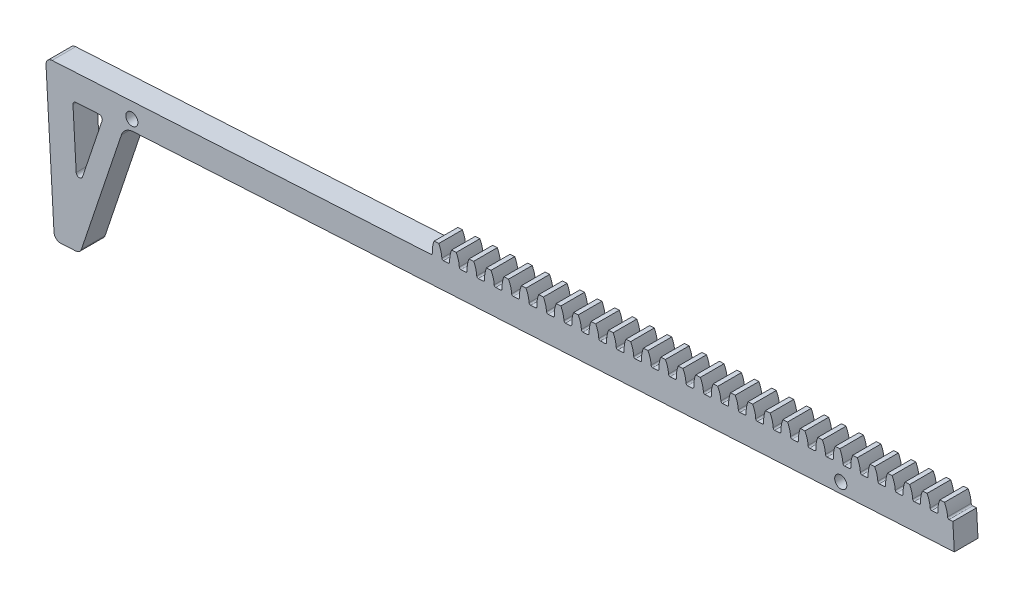
SolidWorks part; units mm, degrees
ref_plane "Front Plane" through (0, 0, 0) normal (0, 0, 1) x (1, 0, 0)
ref_plane "Top Plane" through (0, 0, 0) normal (0, 1, 0) x (1, 0, 0)
ref_plane "Right Plane" through (0, 0, 0) normal (1, 0, 0) x (0, 0, -1)
sketch "Sketch1" plane through (0, 0, 0) normal (0, 0, 1) x (1, 0, 0)
  circle A0 centre (0, 0) radius 23.4
  circle A1 centre (0, 0) radius 24.7
  circle A2 centre (0, 0) radius 21.58
  dimension "D1" = 46.8
  dimension "D2" = 49.4
  dimension "D3" = 3.12
extrude "Boss-Extrude1" add sketch "Sketch1" along normal mid plane 5.642 contours A2 | A0 A2 | A1 A0 region at (-22.7381, 0, 0) region at (-24.0014, 0, 0) region at (0, 0, 0)
sketch "Sketch3" plane through (0, 0, 2.821) normal (0, 0, 1) x (1, 0, 0)
  line L0 (0, 0) -> (0, 24.7) construction
  line L1 (-1.0207, 23.3777) -> (1.0207, 23.3777) construction
  line L2 (0, 0) -> (-0.7079, 21.5684) construction
  line L3 (0, 20.5885) -> (-1.8365, 25.6343) construction
  line L4 (0, 0) -> (2.1527, 24.606) construction
  line L5 (1.0207, 23.3777) -> (3.0543, 23.1998) construction
  circle A0 centre (0, 0) radius 24.7 construction
  arc A1 (-2.2399, 25.6022) -> (-0.7079, 21.5684) centre (-7.3591, 21.3501) cw
  arc A2 (2.2399, 25.6022) -> (0.7079, 21.5684) centre (7.3591, 21.3501) ccw
  circle A3 centre (0, 0) radius 21.58 construction
  arc A4 (0.7079, 21.5684) -> (-0.7079, 21.5684) centre (0, 0) ccw
  circle A6 centre (0, 0) radius 23.4 construction
  circle A7 centre (0, 0) radius 25.7
  arc A8 (2.2399, 25.6022) -> (-2.2399, 25.6022) centre (0, 0) ccw
  circle A9 centre (0, 0) radius 24.7 construction
  point P20 (2.0375, 23.2888)
  dimension "D2" = 20
  dimension "D3" = 5
sketch "Sketch4" plane through (0, 0, 0) normal (0, 1, 0) x (1, 0, 0)
  line L0 (0.7559, -2.821) -> (-0.7559, 2.821)
  line L1 (-24.7, -2.821) -> (24.7, -2.821) construction
  line L2 (24.7, 2.821) -> (-24.7, 2.821) construction
  line L3 (0, -3.2131) -> (0, 3.2131) construction
  dimension "D1" = 15
curve "Curve1"
sketch "Sketch5" plane through (0, 0, 2.821) normal (0, 0, 1) x (0.9995, -0.0306, 0)
  line L0 (0, 0) -> (0, 24.7) construction
  line L1 (-1.0207, 23.3777) -> (1.0207, 23.3777) construction
  line L2 (0, 0) -> (-0.7079, 21.5684) construction
  line L3 (0, 20.5885) -> (-1.8365, 25.6343) construction
  line L4 (0, 0) -> (2.1527, 24.606) construction
  line L5 (1.0207, 23.3777) -> (3.0543, 23.1998) construction
  arc A1 (-2.2399, 25.6022) -> (-0.7079, 21.5684) centre (-7.3591, 21.3501) cw
  arc A2 (2.2399, 25.6022) -> (0.7079, 21.5684) centre (7.3591, 21.3501) ccw
  arc A4 (0.7079, 21.5684) -> (-0.7079, 21.5684) centre (0, 0) ccw
  arc A8 (2.2399, 25.6022) -> (-2.2399, 25.6022) centre (0, 0) ccw
  point P20 (2.0375, 23.2888)
sketch "Sketch7" [suppressed] plane through (1.6622, 0.2826, -4.7625) normal (0, 0, 1) x (0.9724, 0.2332, 0)
  line L0 (0, 0) -> (0, 12.6) construction
  line L1 (-1.4097, 10.7076) -> (1.4097, 10.7076) construction
  line L2 (0, 0) -> (-0.707, 8.2498) construction
  line L3 (0, 6.9803) -> (-2.3358, 13.3979) construction
  line L4 (0, 0) -> (3.2611, 12.1707) construction
  line L5 (1.4097, 10.7076) -> (4.133, 9.9779) construction
  arc A1 (-3.5199, 13.1366) -> (-0.707, 8.2498) centre (-7.3467, 7.6808) cw
  arc A2 (3.5199, 13.1366) -> (0.707, 8.2498) centre (7.3467, 7.6808) ccw
  arc A4 (0.707, 8.2498) -> (-0.707, 8.2498) centre (0, 0) ccw
  arc A8 (3.5199, 13.1366) -> (-3.5199, 13.1366) centre (0, 0) ccw
  point P20 (2.7713, 10.3428)
loft "Cut-Loft1" [suppressed] cut profiles "Sketch7", "Sketch3" end constraint default
fillet "Fillet2" [suppressed] radius 0.39
pattern_circular "CirPattern2" [suppressed] count 36 over 360 of bodies 104
sketch "Sketch8" plane through (0, 0, 2.821) normal (0, 0, 1) x (1, 0, 0)
  line L0 (0, 24.7) -> (0, -24.7) construction
  line L1 (0, 0) -> (7.9375, 0) construction
  circle A0 centre (0, 0) radius 7.9375
  circle A1 centre (0, 0) radius 24.7 construction
  circle A2 centre (0, 13.5) radius 1.7526
  circle A3 centre (11.6913, 6.75) radius 1.7526
  circle A4 centre (11.6913, -6.75) radius 1.7526
  circle A5 centre (0, -13.5) radius 1.7526
  circle A6 centre (-11.6913, -6.75) radius 1.7526
  circle A7 centre (-11.6913, 6.75) radius 1.7526
  spline S0 degree 3 poles (-0.7559, 24.6884) (-0.252, 24.7039) (0.252, 24.7039) (0.7559, 24.6884) knots 0 0 0 0 1 1 1 1 weights 1 0.999688 0.999688 1 construction
  point P26 (0, 0)
  dimension "D1" = 15.875
  dimension "D2" = 13.5
  dimension "D3" = 3.5052
  dimension "D4" = 6
extrude "Cut-Extrude1" cut sketch "Sketch8" against normal through all
extrude "Cut-Extrude2" cut sketch "Sketch5" against normal through all
fillet "Fillet3" radius 0.39 2 edges at (-0.0475, 21.5799, 0) (1.3676, 21.5366, 0)
pattern_circular "CirPattern3" count 36 over 360 about axis through (0, 0, 2.821) along (0, 0, -1) of "Cut-Extrude2", "Fillet3"
sketch "Sketch9" plane through (0, 0, 2.821) normal (0, 0, 1) x (1, 0, 0)
  line L0 (0, 0) -> (0, 11.1125) construction
  line L1 (0, 0) -> (9.6237, 5.5563) construction
  circle A0 centre (0, 0) radius 11.1125 construction
  circle A1 centre (0, 0) radius 19.05 construction
  circle A2 centre (0, 13.5) radius 2.994
  circle A3 centre (11.6913, 6.75) radius 2.994
  circle A4 centre (11.6913, -6.75) radius 2.994
  circle A5 centre (0, -13.5) radius 2.994
  circle A6 centre (-11.6913, -6.75) radius 2.994
  circle A7 centre (-11.6913, 6.75) radius 2.994
  point P23 (0, 0)
  dimension "D1" = 22.225
  dimension "D3" = 5.988
  dimension "D2" = 7.9375
  dimension "D4" = 6
extrude "Cut-Extrude3" cut sketch "Sketch9" against normal blind 1.292
chamfer "Chamfer1" distance 0.2 angle 45 8 edges at (7.9375, 0, 2.821) (7.9375, 0, -2.821) (-9.9387, -6.75, 1.529) (1.7526, -13.5, 1.529) (13.4439, -6.75, 1.529) (13.4439, 6.75, 1.529) (1.7526, 13.5, 1.529) (-9.9387, 6.75, 1.529)
sketch "Sketch11" plane through (0, 0, 2.821) normal (0, 0, 1) x (1, 0, 0)
  line L0 (-2.4235, 21.8111) -> (-0.0583, 21.9452) construction
  line L1 (0.3252, 21.5775) -> (1.541, 21.6465)
  line L2 (4.6292, 21.8217) -> (5.8451, 21.8906)
  line L3 (8.9332, 22.0658) -> (10.1491, 22.1348)
  line L4 (13.2372, 22.3099) -> (14.4531, 22.3789)
  line L5 (17.5413, 22.554) -> (18.7571, 22.623)
  line L6 (21.8453, 22.7982) -> (23.0612, 22.8671)
  line L7 (26.1493, 23.0423) -> (27.3652, 23.1113)
  line L8 (30.4533, 23.2864) -> (31.6692, 23.3554)
  line L9 (34.7574, 23.5305) -> (35.9732, 23.5995)
  line L10 (39.0614, 23.7747) -> (40.2773, 23.8436)
  line L11 (43.3654, 24.0188) -> (44.5813, 24.0877)
  line L12 (47.6695, 24.2629) -> (48.8853, 24.3319)
  line L13 (51.9735, 24.507) -> (53.1893, 24.576)
  line L14 (56.2775, 24.7512) -> (57.4934, 24.8201)
  line L15 (60.5815, 24.9953) -> (61.7974, 25.0642)
  line L16 (64.8856, 25.2394) -> (66.1014, 25.3084)
  line L17 (69.1896, 25.4835) -> (70.4054, 25.5525)
  line L18 (73.4936, 25.7276) -> (74.7095, 25.7966)
  line L19 (77.7976, 25.9718) -> (79.0135, 26.0407)
  line L20 (82.1017, 26.2159) -> (83.3175, 26.2849)
  line L21 (86.4057, 26.46) -> (87.6215, 26.529)
  line L22 (90.7097, 26.7041) -> (91.9256, 26.7731)
  line L23 (95.0137, 26.9483) -> (96.2296, 27.0172)
  line L24 (99.3178, 27.1924) -> (100.5336, 27.2613)
  line L25 (103.6218, 27.4365) -> (104.8376, 27.5055)
  line L26 (107.9258, 27.6806) -> (109.1417, 27.7496)
  line L27 (112.2298, 27.9248) -> (113.4457, 27.9937)
  line L28 (116.5339, 28.1689) -> (117.7497, 28.2378)
  line L29 (120.8379, 28.413) -> (122.0537, 28.482)
  line L30 (125.1419, 28.6571) -> (126.3578, 28.7261)
  line L31 (129.4459, 28.9012) -> (130.6618, 28.9702)
  line L32 (133.75, 29.1454) -> (134.9658, 29.2143)
  line L33 (138.054, 29.3895) -> (139.2698, 29.4585)
  line L34 (142.358, 29.6336) -> (143.5739, 29.7026)
  line L35 (146.662, 29.8777) -> (147.8779, 29.9467)
  line L36 (150.9661, 30.1219) -> (152.1819, 30.1908)
  line L37 (-2.763, 21.4024) -> (-2.4034, 15.0626)
  line L38 (155.2701, 30.366) -> (156.4859, 30.435)
  line L39 (159.5741, 30.6101) -> (160.79, 30.6791)
  line L40 (163.8781, 30.8542) -> (165.094, 30.9232)
  line L41 (168.1822, 31.0984) -> (169.398, 31.1673)
  line L42 (172.4862, 31.3425) -> (173.702, 31.4114)
  line L43 (-2.4034, 15.0626) -> (177.1498, 25.2468)
  line L44 (177.1498, 25.2468) -> (176.7902, 31.5866)
  arc A0 (1.541, 21.6465) -> (1.8805, 22.0552) centre (1.4911, 22.0333) ccw
  arc A1 (2.332, 24.8653) -> (1.8805, 22.0552) centre (8.5248, 22.429) ccw
  arc A2 (3.4794, 24.9304) -> (2.332, 24.8653) centre (4.304, 0.2441) ccw
  arc A3 (4.2457, 22.1894) -> (3.4794, 24.9304) centre (-2.3982, 21.8094) ccw
  arc A4 (4.2457, 22.1894) -> (4.6292, 21.8217) centre (4.6351, 22.2116) ccw
  arc A5 (5.8451, 21.8906) -> (6.1845, 22.2993) centre (5.7951, 22.2774) ccw
  arc A6 (6.636, 25.1094) -> (6.1845, 22.2993) centre (12.8288, 22.6731) ccw
  arc A7 (7.7834, 25.1745) -> (6.636, 25.1094) centre (8.6081, 0.4882) ccw
  arc A8 (8.5497, 22.4335) -> (7.7834, 25.1745) centre (1.9058, 22.0536) ccw
  arc A9 (8.5497, 22.4335) -> (8.9332, 22.0658) centre (8.9391, 22.4558) ccw
  arc A10 (10.1491, 22.1348) -> (10.4885, 22.5435) centre (10.0992, 22.5215) ccw
  arc A11 (10.94, 25.3535) -> (10.4885, 22.5435) centre (17.1328, 22.9172) ccw
  arc A12 (12.0874, 25.4186) -> (10.94, 25.3535) centre (12.9121, 0.7324) ccw
  arc A13 (12.8538, 22.6776) -> (12.0874, 25.4186) centre (6.2098, 22.2977) ccw
  arc A14 (12.8538, 22.6776) -> (13.2372, 22.3099) centre (13.2431, 22.6999) ccw
  arc A15 (14.4531, 22.3789) -> (14.7926, 22.7876) centre (14.4032, 22.7657) ccw
  arc A16 (15.2441, 25.5976) -> (14.7926, 22.7876) centre (21.4368, 23.1613) ccw
  arc A17 (16.3914, 25.6627) -> (15.2441, 25.5976) centre (17.2161, 0.9765) ccw
  arc A18 (17.1578, 22.9217) -> (16.3914, 25.6627) centre (10.5139, 22.5418) ccw
  arc A19 (17.1578, 22.9217) -> (17.5413, 22.554) centre (17.5472, 22.944) ccw
  arc A20 (18.7571, 22.623) -> (19.0966, 23.0317) centre (18.7072, 23.0098) ccw
  arc A21 (19.5481, 25.8418) -> (19.0966, 23.0317) centre (25.7409, 23.4055) ccw
  arc A22 (20.6955, 25.9068) -> (19.5481, 25.8418) centre (21.5201, 1.2206) ccw
  arc A23 (21.4618, 23.1659) -> (20.6955, 25.9068) centre (14.8179, 22.7859) ccw
  arc A24 (21.4618, 23.1659) -> (21.8453, 22.7982) centre (21.8512, 23.1881) ccw
  arc A25 (23.0612, 22.8671) -> (23.4006, 23.2758) centre (23.0112, 23.2539) ccw
  arc A26 (23.8521, 26.0859) -> (23.4006, 23.2758) centre (30.0449, 23.6496) ccw
  arc A27 (24.9995, 26.151) -> (23.8521, 26.0859) centre (25.8242, 1.4647) ccw
  arc A28 (25.7658, 23.41) -> (24.9995, 26.151) centre (19.1219, 23.03) ccw
  arc A29 (25.7658, 23.41) -> (26.1493, 23.0423) centre (26.1552, 23.4322) ccw
  arc A30 (27.3652, 23.1113) -> (27.7046, 23.5199) centre (27.3153, 23.498) ccw
  arc A31 (28.1561, 26.33) -> (27.7046, 23.5199) centre (34.3489, 23.8937) ccw
  arc A32 (29.3035, 26.3951) -> (28.1561, 26.33) centre (30.1282, 1.7089) ccw
  arc A33 (30.0699, 23.6541) -> (29.3035, 26.3951) centre (23.4259, 23.2742) ccw
  arc A34 (30.0699, 23.6541) -> (30.4533, 23.2864) centre (30.4592, 23.6764) ccw
  arc A35 (31.6692, 23.3554) -> (32.0087, 23.7641) centre (31.6193, 23.7422) ccw
  arc A36 (32.4602, 26.5741) -> (32.0087, 23.7641) centre (38.6529, 24.1378) ccw
  arc A37 (33.6075, 26.6392) -> (32.4602, 26.5741) centre (34.4322, 1.953) ccw
  arc A38 (34.3739, 23.8982) -> (33.6075, 26.6392) centre (27.73, 23.5183) ccw
  arc A39 (34.3739, 23.8982) -> (34.7574, 23.5305) centre (34.7633, 23.9205) ccw
  arc A40 (35.9732, 23.5995) -> (36.3127, 24.0082) centre (35.9233, 23.9863) ccw
  arc A41 (36.7642, 26.8183) -> (36.3127, 24.0082) centre (42.957, 24.382) ccw
  arc A42 (37.9116, 26.8833) -> (36.7642, 26.8183) centre (38.7362, 2.1971) ccw
  arc A43 (38.6779, 24.1423) -> (37.9116, 26.8833) centre (32.034, 23.7624) ccw
  arc A44 (38.6779, 24.1423) -> (39.0614, 23.7747) centre (39.0673, 24.1646) ccw
  arc A45 (40.2773, 23.8436) -> (40.6167, 24.2523) centre (40.2273, 24.2304) ccw
  arc A46 (41.0682, 27.0624) -> (40.6167, 24.2523) centre (47.261, 24.6261) ccw
  arc A47 (42.2156, 27.1275) -> (41.0682, 27.0624) centre (43.0403, 2.4412) ccw
  arc A48 (42.9819, 24.3865) -> (42.2156, 27.1275) centre (36.338, 24.0065) ccw
  arc A49 (42.9819, 24.3865) -> (43.3654, 24.0188) centre (43.3713, 24.4087) ccw
  arc A50 (44.5813, 24.0877) -> (44.9207, 24.4964) centre (44.5314, 24.4745) ccw
  arc A51 (45.3722, 27.3065) -> (44.9207, 24.4964) centre (51.565, 24.8702) ccw
  arc A52 (46.5196, 27.3716) -> (45.3722, 27.3065) centre (47.3443, 2.6854) ccw
  arc A53 (47.286, 24.6306) -> (46.5196, 27.3716) centre (40.642, 24.2507) ccw
  arc A54 (47.286, 24.6306) -> (47.6695, 24.2629) centre (47.6753, 24.6529) ccw
  arc A55 (48.8853, 24.3319) -> (49.2248, 24.7406) centre (48.8354, 24.7187) ccw
  arc A56 (49.6763, 27.5506) -> (49.2248, 24.7406) centre (55.869, 25.1143) ccw
  arc A57 (50.8236, 27.6157) -> (49.6763, 27.5506) centre (51.6483, 2.9295) ccw
  arc A58 (51.59, 24.8747) -> (50.8236, 27.6157) centre (44.9461, 24.4948) ccw
  arc A59 (51.59, 24.8747) -> (51.9735, 24.507) centre (51.9794, 24.897) ccw
  arc A60 (53.1893, 24.576) -> (53.5288, 24.9847) centre (53.1394, 24.9628) ccw
  arc A61 (53.9803, 27.7948) -> (53.5288, 24.9847) centre (60.1731, 25.3585) ccw
  arc A62 (55.1277, 27.8598) -> (53.9803, 27.7948) centre (55.9523, 3.1736) ccw
  arc A63 (55.894, 25.1188) -> (55.1277, 27.8598) centre (49.2501, 24.7389) ccw
  arc A64 (55.894, 25.1188) -> (56.2775, 24.7512) centre (56.2834, 25.1411) ccw
  arc A65 (57.4934, 24.8201) -> (57.8328, 25.2288) centre (57.4434, 25.2069) ccw
  arc A66 (58.2843, 28.0389) -> (57.8328, 25.2288) centre (64.4771, 25.6026) ccw
  arc A67 (59.4317, 28.104) -> (58.2843, 28.0389) centre (60.2564, 3.4177) ccw
  arc A68 (60.198, 25.363) -> (59.4317, 28.104) centre (53.5541, 24.983) ccw
  arc A69 (60.198, 25.363) -> (60.5815, 24.9953) centre (60.5874, 25.3852) ccw
  arc A70 (61.7974, 25.0642) -> (62.1368, 25.4729) centre (61.7475, 25.451) ccw
  arc A71 (62.5883, 28.283) -> (62.1368, 25.4729) centre (68.7811, 25.8467) ccw
  arc A72 (63.7357, 28.3481) -> (62.5883, 28.283) centre (64.5604, 3.6618) ccw
  arc A73 (64.5021, 25.6071) -> (63.7357, 28.3481) centre (57.8581, 25.2272) ccw
  arc A74 (64.5021, 25.6071) -> (64.8856, 25.2394) centre (64.8914, 25.6294) ccw
  arc A75 (66.1014, 25.3084) -> (66.4409, 25.7171) centre (66.0515, 25.6952) ccw
  arc A76 (66.8924, 28.5271) -> (66.4409, 25.7171) centre (73.0851, 26.0908) ccw
  arc A77 (68.0397, 28.5922) -> (66.8924, 28.5271) centre (68.8644, 3.906) ccw
  arc A78 (68.8061, 25.8512) -> (68.0397, 28.5922) centre (62.1622, 25.4713) ccw
  arc A79 (68.8061, 25.8512) -> (69.1896, 25.4835) centre (69.1955, 25.8735) ccw
  arc A80 (70.4054, 25.5525) -> (70.7449, 25.9612) centre (70.3555, 25.9393) ccw
  arc A81 (71.1964, 28.7712) -> (70.7449, 25.9612) centre (77.3892, 26.335) ccw
  arc A82 (72.3438, 28.8363) -> (71.1964, 28.7712) centre (73.1684, 4.1501) ccw
  arc A83 (73.1101, 26.0953) -> (72.3438, 28.8363) centre (66.4662, 25.7154) ccw
  arc A84 (73.1101, 26.0953) -> (73.4936, 25.7276) centre (73.4995, 26.1176) ccw
  arc A85 (74.7095, 25.7966) -> (75.0489, 26.2053) centre (74.6595, 26.1834) ccw
  arc A86 (75.5004, 29.0154) -> (75.0489, 26.2053) centre (81.6932, 26.5791) ccw
  arc A87 (76.6478, 29.0804) -> (75.5004, 29.0154) centre (77.4725, 4.3942) ccw
  arc A88 (77.4141, 26.3395) -> (76.6478, 29.0804) centre (70.7702, 25.9595) ccw
  arc A89 (77.4141, 26.3395) -> (77.7976, 25.9718) centre (77.8035, 26.3617) ccw
  arc A90 (79.0135, 26.0407) -> (79.3529, 26.4494) centre (78.9636, 26.4275) ccw
  arc A91 (79.8044, 29.2595) -> (79.3529, 26.4494) centre (85.9972, 26.8232) ccw
  arc A92 (80.9518, 29.3246) -> (79.8044, 29.2595) centre (81.7765, 4.6383) ccw
  arc A93 (81.7182, 26.5836) -> (80.9518, 29.3246) centre (75.0742, 26.2036) ccw
  arc A94 (81.7182, 26.5836) -> (82.1017, 26.2159) centre (82.1075, 26.6058) ccw
  arc A95 (83.3175, 26.2849) -> (83.657, 26.6936) centre (83.2676, 26.6716) ccw
  arc A96 (84.1085, 29.5036) -> (83.657, 26.6936) centre (90.3012, 27.0673) ccw
  arc A97 (85.2558, 29.5687) -> (84.1085, 29.5036) centre (86.0805, 4.8825) ccw
  arc A98 (86.0222, 26.8277) -> (85.2558, 29.5687) centre (79.3783, 26.4478) ccw
  arc A99 (86.0222, 26.8277) -> (86.4057, 26.46) centre (86.4116, 26.85) ccw
  arc A100 (87.6215, 26.529) -> (87.961, 26.9377) centre (87.5716, 26.9158) ccw
  arc A101 (88.4125, 29.7477) -> (87.961, 26.9377) centre (94.6053, 27.3114) ccw
  arc A102 (89.5599, 29.8128) -> (88.4125, 29.7477) centre (90.3845, 5.1266) ccw
  arc A103 (90.3262, 27.0718) -> (89.5599, 29.8128) centre (83.6823, 26.6919) ccw
  arc A104 (90.3262, 27.0718) -> (90.7097, 26.7041) centre (90.7156, 27.0941) ccw
  arc A105 (91.9256, 26.7731) -> (92.265, 27.1818) centre (91.8756, 27.1599) ccw
  arc A106 (92.7165, 29.9919) -> (92.265, 27.1818) centre (98.9093, 27.5556) ccw
  arc A107 (93.8639, 30.0569) -> (92.7165, 29.9919) centre (94.6886, 5.3707) ccw
  arc A108 (94.6302, 27.316) -> (93.8639, 30.0569) centre (87.9863, 26.936) ccw
  arc A109 (94.6302, 27.316) -> (95.0137, 26.9483) centre (95.0196, 27.3382) ccw
  arc A110 (96.2296, 27.0172) -> (96.569, 27.4259) centre (96.1797, 27.404) ccw
  arc A111 (97.0205, 30.236) -> (96.569, 27.4259) centre (103.2133, 27.7997) ccw
  arc A112 (98.1679, 30.3011) -> (97.0205, 30.236) centre (98.9926, 5.6148) ccw
  arc A113 (98.9343, 27.5601) -> (98.1679, 30.3011) centre (92.2903, 27.1801) ccw
  arc A114 (98.9343, 27.5601) -> (99.3178, 27.1924) centre (99.3236, 27.5823) ccw
  arc A115 (100.5336, 27.2613) -> (100.8731, 27.67) centre (100.4837, 27.6481) ccw
  arc A116 (101.3246, 30.4801) -> (100.8731, 27.67) centre (107.5173, 28.0438) ccw
  arc A117 (102.4719, 30.5452) -> (101.3246, 30.4801) centre (103.2966, 5.859) ccw
  arc A118 (103.2383, 27.8042) -> (102.4719, 30.5452) centre (96.5944, 27.4243) ccw
  arc A119 (103.2383, 27.8042) -> (103.6218, 27.4365) centre (103.6277, 27.8265) ccw
  arc A120 (104.8376, 27.5055) -> (105.1771, 27.9142) centre (104.7877, 27.8923) ccw
  arc A121 (105.6286, 30.7242) -> (105.1771, 27.9142) centre (111.8214, 28.2879) ccw
  arc A122 (106.776, 30.7893) -> (105.6286, 30.7242) centre (107.6006, 6.1031) ccw
  arc A123 (107.5423, 28.0483) -> (106.776, 30.7893) centre (100.8984, 27.6684) ccw
  arc A124 (107.5423, 28.0483) -> (107.9258, 27.6806) centre (107.9317, 28.0706) ccw
  arc A125 (109.1417, 27.7496) -> (109.4811, 28.1583) centre (109.0917, 28.1364) ccw
  arc A126 (109.9326, 30.9684) -> (109.4811, 28.1583) centre (116.1254, 28.5321) ccw
  arc A127 (111.08, 31.0334) -> (109.9326, 30.9684) centre (111.9047, 6.3472) ccw
  arc A128 (111.8463, 28.2924) -> (111.08, 31.0334) centre (105.2024, 27.9125) ccw
  arc A129 (111.8463, 28.2924) -> (112.2298, 27.9248) centre (112.2357, 28.3147) ccw
  arc A130 (113.4457, 27.9937) -> (113.7851, 28.4024) centre (113.3958, 28.3805) ccw
  arc A131 (114.2366, 31.2125) -> (113.7851, 28.4024) centre (120.4294, 28.7762) ccw
  arc A132 (115.384, 31.2776) -> (114.2366, 31.2125) centre (116.2087, 6.5913) ccw
  arc A133 (116.1504, 28.5366) -> (115.384, 31.2776) centre (109.5064, 28.1566) ccw
  arc A134 (116.1504, 28.5366) -> (116.5339, 28.1689) centre (116.5397, 28.5588) ccw
  arc A135 (117.7497, 28.2378) -> (118.0892, 28.6465) centre (117.6998, 28.6246) ccw
  arc A136 (118.5407, 31.4566) -> (118.0892, 28.6465) centre (124.7334, 29.0203) ccw
  arc A137 (119.688, 31.5217) -> (118.5407, 31.4566) centre (120.5127, 6.8355) ccw
  arc A138 (120.4544, 28.7807) -> (119.688, 31.5217) centre (113.8105, 28.4008) ccw
  arc A139 (120.4544, 28.7807) -> (120.8379, 28.413) centre (120.8438, 28.803) ccw
  arc A140 (122.0537, 28.482) -> (122.3932, 28.8907) centre (122.0038, 28.8688) ccw
  arc A141 (122.8447, 31.7007) -> (122.3932, 28.8907) centre (129.0375, 29.2644) ccw
  arc A142 (123.9921, 31.7658) -> (122.8447, 31.7007) centre (124.8167, 7.0796) ccw
  arc A143 (124.7584, 29.0248) -> (123.9921, 31.7658) centre (118.1145, 28.6449) ccw
  arc A144 (124.7584, 29.0248) -> (125.1419, 28.6571) centre (125.1478, 29.0471) ccw
  arc A145 (126.3578, 28.7261) -> (126.6972, 29.1348) centre (126.3078, 29.1129) ccw
  arc A146 (127.1487, 31.9448) -> (126.6972, 29.1348) centre (133.3415, 29.5086) ccw
  arc A147 (128.2961, 32.0099) -> (127.1487, 31.9448) centre (129.1208, 7.3237) ccw
  arc A148 (129.0624, 29.2689) -> (128.2961, 32.0099) centre (122.4185, 28.889) ccw
  arc A149 (129.0624, 29.2689) -> (129.4459, 28.9012) centre (129.4518, 29.2912) ccw
  arc A150 (130.6618, 28.9702) -> (131.0012, 29.3789) centre (130.6119, 29.357) ccw
  arc A151 (131.4527, 32.189) -> (131.0012, 29.3789) centre (137.6455, 29.7527) ccw
  arc A152 (132.6001, 32.2541) -> (131.4527, 32.189) centre (133.4248, 7.5678) ccw
  arc A153 (133.3665, 29.5131) -> (132.6001, 32.2541) centre (126.7225, 29.1331) ccw
  arc A154 (133.3665, 29.5131) -> (133.75, 29.1454) centre (133.7558, 29.5353) ccw
  arc A155 (134.9658, 29.2143) -> (135.3053, 29.623) centre (134.9159, 29.6011) ccw
  arc A156 (135.7568, 32.4331) -> (135.3053, 29.623) centre (141.9495, 29.9968) ccw
  arc A157 (136.9041, 32.4982) -> (135.7568, 32.4331) centre (137.7288, 7.8119) ccw
  arc A158 (137.6705, 29.7572) -> (136.9041, 32.4982) centre (131.0266, 29.3773) ccw
  arc A159 (137.6705, 29.7572) -> (138.054, 29.3895) centre (138.0599, 29.7795) ccw
  arc A160 (139.2698, 29.4585) -> (139.6093, 29.8672) centre (139.2199, 29.8452) ccw
  arc A161 (140.0608, 32.6772) -> (139.6093, 29.8672) centre (146.2536, 30.2409) ccw
  arc A162 (141.2082, 32.7423) -> (140.0608, 32.6772) centre (142.0328, 8.0561) ccw
  arc A163 (141.9745, 30.0013) -> (141.2082, 32.7423) centre (135.3306, 29.6214) ccw
  arc A164 (141.9745, 30.0013) -> (142.358, 29.6336) centre (142.3639, 30.0236) ccw
  arc A165 (143.5739, 29.7026) -> (143.9133, 30.1113) centre (143.5239, 30.0894) ccw
  arc A166 (144.3648, 32.9213) -> (143.9133, 30.1113) centre (150.5576, 30.485) ccw
  arc A167 (145.5122, 32.9864) -> (144.3648, 32.9213) centre (146.3369, 8.3002) ccw
  arc A168 (146.2785, 30.2454) -> (145.5122, 32.9864) centre (139.6346, 29.8655) ccw
  arc A169 (146.2785, 30.2454) -> (146.662, 29.8777) centre (146.6679, 30.2677) ccw
  arc A170 (147.8779, 29.9467) -> (148.2173, 30.3554) centre (147.828, 30.3335) ccw
  arc A171 (148.6688, 33.1655) -> (148.2173, 30.3554) centre (154.8616, 30.7292) ccw
  arc A172 (149.8162, 33.2305) -> (148.6688, 33.1655) centre (150.6409, 8.5443) ccw
  arc A173 (150.5826, 30.4896) -> (149.8162, 33.2305) centre (143.9386, 30.1096) ccw
  arc A174 (150.5826, 30.4896) -> (150.9661, 30.1219) centre (150.9719, 30.5118) ccw
  arc A175 (152.1819, 30.1908) -> (152.5214, 30.5995) centre (152.132, 30.5776) ccw
  arc A176 (152.9729, 33.4096) -> (152.5214, 30.5995) centre (159.1656, 30.9733) ccw
  arc A177 (154.1202, 33.4747) -> (152.9729, 33.4096) centre (154.9449, 8.7884) ccw
  arc A178 (154.8866, 30.7337) -> (154.1202, 33.4747) centre (148.2427, 30.3537) ccw
  arc A179 (154.8866, 30.7337) -> (155.2701, 30.366) centre (155.276, 30.7559) ccw
  arc A180 (156.4859, 30.435) -> (156.8254, 30.8436) centre (156.436, 30.8217) ccw
  arc A181 (157.2769, 33.6537) -> (156.8254, 30.8436) centre (163.4697, 31.2174) ccw
  arc A182 (158.4243, 33.7188) -> (157.2769, 33.6537) centre (159.2489, 9.0326) ccw
  arc A183 (159.1906, 30.9778) -> (158.4243, 33.7188) centre (152.5467, 30.5979) ccw
  arc A184 (159.1906, 30.9778) -> (159.5741, 30.6101) centre (159.58, 31.0001) ccw
  arc A185 (160.79, 30.6791) -> (161.1294, 31.0878) centre (160.74, 31.0659) ccw
  arc A186 (161.5809, 33.8978) -> (161.1294, 31.0878) centre (167.7737, 31.4615) ccw
  arc A187 (162.7283, 33.9629) -> (161.5809, 33.8978) centre (163.553, 9.2767) ccw
  arc A188 (163.4946, 31.2219) -> (162.7283, 33.9629) centre (156.8507, 30.842) ccw
  arc A189 (163.4946, 31.2219) -> (163.8781, 30.8542) centre (163.884, 31.2442) ccw
  arc A190 (165.094, 30.9232) -> (165.4334, 31.3319) centre (165.0441, 31.31) ccw
  arc A191 (165.8849, 34.142) -> (165.4334, 31.3319) centre (172.0777, 31.7057) ccw
  arc A192 (167.0323, 34.207) -> (165.8849, 34.142) centre (167.857, 9.5208) ccw
  arc A193 (167.7987, 31.466) -> (167.0323, 34.207) centre (161.1547, 31.0861) ccw
  arc A194 (167.7987, 31.466) -> (168.1822, 31.0984) centre (168.188, 31.4883) ccw
  arc A195 (169.398, 31.1673) -> (169.7375, 31.576) centre (169.3481, 31.5541) ccw
  arc A196 (170.189, 34.3861) -> (169.7375, 31.576) centre (176.3817, 31.9498) ccw
  arc A197 (171.3363, 34.4512) -> (170.189, 34.3861) centre (172.161, 9.7649) ccw
  arc A198 (172.1027, 31.7102) -> (171.3363, 34.4512) centre (165.4588, 31.3302) ccw
  arc A199 (172.1027, 31.7102) -> (172.4862, 31.3425) centre (172.4921, 31.7324) ccw
  arc A200 (173.702, 31.4114) -> (174.0415, 31.8201) centre (173.6521, 31.7982) ccw
  arc A201 (174.493, 34.6302) -> (174.0415, 31.8201) centre (180.6858, 32.1939) ccw
  arc A202 (175.6404, 34.6953) -> (174.493, 34.6302) centre (176.465, 10.0091) ccw
  arc A203 (176.4067, 31.9543) -> (175.6404, 34.6953) centre (169.7628, 31.5744) ccw
  arc A204 (176.4067, 31.9543) -> (176.7902, 31.5866) centre (176.7961, 31.9766) ccw
  arc A216 (-1.972, 24.6211) -> (-2.4235, 21.8111) centre (4.2207, 22.1849) ccw
  arc A217 (-2.763, 21.4024) -> (-2.4235, 21.8111) centre (-2.8129, 21.7892) ccw
  arc A218 (-2.763, 21.4024) -> (-3.4267, 21.3062) centre (0, 0) ccw
  arc A219 (-3.8682, 21.6017) -> (-3.4267, 21.3062) centre (-3.4886, 21.6913) ccw
  arc A220 (-3.8682, 21.6017) -> (-5.0988, 24.168) centre (-10.3452, 20.0738) ccw
  arc A221 (-5.0988, 24.168) -> (-6.2175, 23.9047) centre (0, 0) ccw
  arc A222 (-6.2175, 23.9047) -> (-6.1742, 21.0589) centre (0.3043, 22.5807) ccw
  arc A223 (-6.4375, 20.5975) -> (-6.1742, 21.0589) centre (-6.5538, 20.9697) ccw
  arc A224 (-6.4375, 20.5975) -> (-7.0744, 20.3875) centre (0, 0) ccw
  arc A225 (-7.5605, 20.6018) -> (-7.0744, 20.3875) centre (-7.2022, 20.7559) ccw
  arc A226 (-7.5605, 20.6018) -> (-9.2181, 22.9154) centre (-13.6738, 17.9725) ccw
  arc A227 (-9.2181, 22.9154) -> (-10.274, 22.4618) centre (0, 0) ccw
  arc A228 (-10.274, 22.4618) -> (-9.7372, 19.6668) centre (-3.6215, 22.2905) ccw
  arc A229 (-9.9164, 19.1667) -> (-9.7372, 19.6668) centre (-10.0956, 19.5131) ccw
  arc A230 (-9.9164, 19.1667) -> (-10.5072, 18.8493) centre (0, 0) ccw
  arc A231 (-11.0231, 18.976) -> (-10.5072, 18.8493) centre (-10.6971, 19.1899) ccw
  arc A232 (-11.0231, 18.976) -> (-13.0573, 20.9666) centre (-16.587, 15.325) ccw
  arc A233 (-13.0573, 20.9666) -> (-14.0184, 20.3365) centre (0, 0) ccw
  arc A234 (-14.0184, 20.3365) -> (-13.0044, 17.6772) centre (-7.4372, 21.323) ccw
  arc A235 (-13.094, 17.1535) -> (-13.0044, 17.6772) centre (-13.3306, 17.4635) ccw
  arc A236 (-13.094, 17.1535) -> (-13.6207, 16.7384) centre (0, 0) ccw
  arc A237 (-14.1508, 16.7735) -> (-13.6207, 16.7384) centre (-13.8668, 17.0409) ccw
  arc A238 (-14.1508, 16.7735) -> (-16.4997, 18.3807) centre (-18.9961, 12.2119) ccw
  arc A239 (-16.4997, 18.3807) -> (-17.3368, 17.5933) centre (0, 0) ccw
  arc A240 (-17.3368, 17.5933) -> (-15.8764, 15.1504) centre (-11.0269, 19.7076) ccw
  arc A241 (-15.8738, 14.6192) -> (-15.8764, 15.1504) centre (-16.1606, 14.8834) ccw
  arc A242 (-15.8738, 14.6192) -> (-16.3203, 14.1189) centre (0, 0) ccw
  arc A243 (-16.8485, 14.0615) -> (-16.3203, 14.1189) centre (-16.6153, 14.374) ccw
  arc A244 (-16.8485, 14.0615) -> (-19.4408, 15.2363) centre (-20.8281, 8.7277) ccw
  arc A245 (-19.4408, 15.2363) -> (-20.1285, 14.3155) centre (0, 0) ccw
  arc A246 (-20.1285, 14.3155) -> (-18.2661, 12.1634) centre (-14.2815, 17.4934) ccw
  arc A247 (-18.1712, 11.6406) -> (-18.2661, 12.1634) centre (-18.4996, 11.851) ccw
  arc A248 (-18.1712, 11.6406) -> (-18.5241, 11.0704) centre (0, 0) ccw
  arc A249 (-19.0343, 10.9221) -> (-18.5241, 11.0704) centre (-18.8589, 11.2705) ccw
  arc A250 (-19.0343, 10.9221) -> (-21.7912, 11.6289) centre (-22.0272, 4.9783) ccw
  arc A251 (-21.7912, 11.6289) -> (-22.3086, 10.6027) centre (0, 0) ccw
  arc A252 (-22.3086, 10.6027) -> (-20.1007, 8.8067) centre (-17.1023, 14.7477) ccw
  arc A253 (-19.9165, 8.3084) -> (-20.1007, 8.8067) centre (-20.2764, 8.4585) ccw
  arc A254 (-19.9165, 8.3084) -> (-20.165, 7.6855) centre (0, 0) ccw
  arc A255 (-20.6417, 7.4509) -> (-20.165, 7.6855) centre (-20.5295, 7.8244) ccw
  arc A256 (-20.6417, 7.4509) -> (-23.4795, 7.6683) centre (-22.5571, 1.0777) ccw
  arc A257 (-23.4795, 7.6683) -> (-23.8108, 6.5678) centre (0, 0) ccw
  arc A258 (-23.8108, 6.5678) -> (-21.3246, 5.1825) centre (-19.4034, 11.5539) ccw
  arc A259 (-21.0567, 4.7237) -> (-21.3246, 5.1825) centre (-21.4372, 4.8091) ccw
  arc A260 (-21.0567, 4.7237) -> (-21.1933, 4.0671) centre (0, 0) ccw
  arc A261 (-21.622, 3.7533) -> (-21.1933, 4.0671) centre (-21.5763, 4.1406) ccw
  arc A262 (-21.622, 3.7533) -> (-24.4544, 3.4746) centre (-22.4015, -2.8556) ccw
  arc A263 (-24.4544, 3.4746) -> (-24.5895, 2.3333) centre (0, 0) ccw
  arc A264 (-24.5895, 2.3333) -> (-21.9006, 1.4007) centre (-21.1149, 8.009) ccw
  arc A265 (-21.557, 0.9955) -> (-21.9006, 1.4007) centre (-21.9466, 1.0135) ccw
  arc A266 (-21.557, 0.9955) -> (-21.5775, 0.3252) centre (0, 0) ccw
  arc A267 (-21.9452, -0.0583) -> (-21.5775, 0.3252) centre (-21.9675, 0.3311) ccw
  arc A268 (-21.9452, -0.0583) -> (-24.6862, -0.8247) centre (-21.5653, -6.7022) ccw
  arc A269 (-24.6862, -0.8247) -> (-24.6211, -1.972) centre (0, 0) ccw
  arc A270 (-24.6211, -1.972) -> (-21.8111, -2.4235) centre (-22.1849, 4.2207) ccw
  arc A271 (-21.4024, -2.763) -> (-21.8111, -2.4235) centre (-21.7892, -2.8129) ccw
  arc A272 (-21.4024, -2.763) -> (-21.3062, -3.4267) centre (0, 0) ccw
  arc A273 (-21.6017, -3.8682) -> (-21.3062, -3.4267) centre (-21.6913, -3.4886) ccw
  arc A274 (-21.6017, -3.8682) -> (-24.168, -5.0988) centre (-20.0738, -10.3452) ccw
  arc A275 (-24.168, -5.0988) -> (-23.9047, -6.2175) centre (0, 0) ccw
  arc A276 (-23.9047, -6.2175) -> (-21.0589, -6.1742) centre (-22.5807, 0.3043) ccw
  arc A277 (-20.5975, -6.4375) -> (-21.0589, -6.1742) centre (-20.9697, -6.5538) ccw
  arc A278 (-20.5975, -6.4375) -> (-20.3875, -7.0744) centre (0, 0) ccw
  arc A279 (-20.6018, -7.5605) -> (-20.3875, -7.0744) centre (-20.7559, -7.2022) ccw
  arc A280 (-20.6018, -7.5605) -> (-22.9154, -9.2181) centre (-17.9725, -13.6738) ccw
  arc A281 (-22.9154, -9.2181) -> (-22.4618, -10.274) centre (0, 0) ccw
  arc A282 (-22.4618, -10.274) -> (-19.6668, -9.7372) centre (-22.2905, -3.6215) ccw
  arc A283 (-19.1667, -9.9164) -> (-19.6668, -9.7372) centre (-19.5131, -10.0956) ccw
  arc A284 (-19.1667, -9.9164) -> (-18.8493, -10.5072) centre (0, 0) ccw
  arc A285 (-18.976, -11.0231) -> (-18.8493, -10.5072) centre (-19.1899, -10.6971) ccw
  arc A286 (-18.976, -11.0231) -> (-20.9666, -13.0573) centre (-15.325, -16.587) ccw
  arc A287 (-20.9666, -13.0573) -> (-20.3365, -14.0184) centre (0, 0) ccw
  arc A288 (-20.3365, -14.0184) -> (-17.6772, -13.0044) centre (-21.323, -7.4372) ccw
  arc A289 (-17.1535, -13.094) -> (-17.6772, -13.0044) centre (-17.4635, -13.3306) ccw
  arc A290 (-17.1535, -13.094) -> (-16.7384, -13.6207) centre (0, 0) ccw
  arc A291 (-16.7735, -14.1508) -> (-16.7384, -13.6207) centre (-17.0409, -13.8668) ccw
  arc A292 (-16.7735, -14.1508) -> (-18.3807, -16.4997) centre (-12.2119, -18.9961) ccw
  arc A293 (-18.3807, -16.4997) -> (-17.5933, -17.3368) centre (0, 0) ccw
  arc A294 (-17.5933, -17.3368) -> (-15.1504, -15.8764) centre (-19.7076, -11.0269) ccw
  arc A295 (-14.6192, -15.8738) -> (-15.1504, -15.8764) centre (-14.8834, -16.1606) ccw
  arc A296 (-14.6192, -15.8738) -> (-14.1189, -16.3203) centre (0, 0) ccw
  arc A297 (-14.0615, -16.8485) -> (-14.1189, -16.3203) centre (-14.374, -16.6153) ccw
  arc A298 (-14.0615, -16.8485) -> (-15.2363, -19.4408) centre (-8.7277, -20.8281) ccw
  arc A299 (-15.2363, -19.4408) -> (-14.3155, -20.1285) centre (0, 0) ccw
  arc A300 (-14.3155, -20.1285) -> (-12.1634, -18.2661) centre (-17.4934, -14.2815) ccw
  arc A301 (-11.6406, -18.1712) -> (-12.1634, -18.2661) centre (-11.851, -18.4996) ccw
  arc A302 (-11.6406, -18.1712) -> (-11.0704, -18.5241) centre (0, 0) ccw
  arc A303 (-10.9221, -19.0343) -> (-11.0704, -18.5241) centre (-11.2705, -18.8589) ccw
  arc A304 (-10.9221, -19.0343) -> (-11.6289, -21.7912) centre (-4.9783, -22.0272) ccw
  arc A305 (-11.6289, -21.7912) -> (-10.6027, -22.3086) centre (0, 0) ccw
  arc A306 (-10.6027, -22.3086) -> (-8.8067, -20.1007) centre (-14.7477, -17.1023) ccw
  arc A307 (-8.3084, -19.9165) -> (-8.8067, -20.1007) centre (-8.4585, -20.2764) ccw
  arc A308 (-8.3084, -19.9165) -> (-7.6855, -20.165) centre (0, 0) ccw
  arc A309 (-7.4509, -20.6417) -> (-7.6855, -20.165) centre (-7.8244, -20.5295) ccw
  arc A310 (-7.4509, -20.6417) -> (-7.6683, -23.4795) centre (-1.0777, -22.5571) ccw
  arc A311 (-7.6683, -23.4795) -> (-6.5678, -23.8108) centre (0, 0) ccw
  arc A312 (-6.5678, -23.8108) -> (-5.1825, -21.3246) centre (-11.5539, -19.4034) ccw
  arc A313 (-4.7237, -21.0567) -> (-5.1825, -21.3246) centre (-4.8091, -21.4372) ccw
  arc A314 (-4.7237, -21.0567) -> (-4.0671, -21.1933) centre (0, 0) ccw
  arc A315 (-3.7533, -21.622) -> (-4.0671, -21.1933) centre (-4.1406, -21.5763) ccw
  arc A316 (-3.7533, -21.622) -> (-3.4746, -24.4544) centre (2.8556, -22.4015) ccw
  arc A317 (-3.4746, -24.4544) -> (-2.3333, -24.5895) centre (0, 0) ccw
  arc A318 (-2.3333, -24.5895) -> (-1.4007, -21.9006) centre (-8.009, -21.1149) ccw
  arc A319 (-0.9955, -21.557) -> (-1.4007, -21.9006) centre (-1.0135, -21.9466) ccw
  arc A320 (-0.9955, -21.557) -> (-0.3252, -21.5775) centre (0, 0) ccw
  arc A321 (0.0583, -21.9452) -> (-0.3252, -21.5775) centre (-0.3311, -21.9675) ccw
  arc A322 (0.0583, -21.9452) -> (0.8247, -24.6862) centre (6.7022, -21.5653) ccw
  arc A323 (0.8247, -24.6862) -> (1.972, -24.6211) centre (0, 0) ccw
  arc A324 (1.972, -24.6211) -> (2.4235, -21.8111) centre (-4.2207, -22.1849) ccw
  arc A325 (2.763, -21.4024) -> (2.4235, -21.8111) centre (2.8129, -21.7892) ccw
  arc A326 (2.763, -21.4024) -> (3.4267, -21.3062) centre (0, 0) ccw
  arc A327 (3.8682, -21.6017) -> (3.4267, -21.3062) centre (3.4886, -21.6913) ccw
  arc A328 (3.8682, -21.6017) -> (5.0988, -24.168) centre (10.3452, -20.0738) ccw
  arc A329 (5.0988, -24.168) -> (6.2175, -23.9047) centre (0, 0) ccw
  arc A330 (6.2175, -23.9047) -> (6.1742, -21.0589) centre (-0.3043, -22.5807) ccw
  arc A331 (6.4375, -20.5975) -> (6.1742, -21.0589) centre (6.5538, -20.9697) ccw
  arc A332 (6.4375, -20.5975) -> (7.0744, -20.3875) centre (0, 0) ccw
  arc A333 (7.5605, -20.6018) -> (7.0744, -20.3875) centre (7.2022, -20.7559) ccw
  arc A334 (7.5605, -20.6018) -> (9.2181, -22.9154) centre (13.6738, -17.9725) ccw
  arc A335 (9.2181, -22.9154) -> (10.274, -22.4618) centre (0, 0) ccw
  arc A336 (10.274, -22.4618) -> (9.7372, -19.6668) centre (3.6215, -22.2905) ccw
  arc A337 (9.9164, -19.1667) -> (9.7372, -19.6668) centre (10.0956, -19.5131) ccw
  arc A338 (9.9164, -19.1667) -> (10.5072, -18.8493) centre (0, 0) ccw
  arc A339 (11.0231, -18.976) -> (10.5072, -18.8493) centre (10.6971, -19.1899) ccw
  arc A340 (11.0231, -18.976) -> (13.0573, -20.9666) centre (16.587, -15.325) ccw
  arc A341 (13.0573, -20.9666) -> (14.0184, -20.3365) centre (0, 0) ccw
  arc A342 (14.0184, -20.3365) -> (13.0044, -17.6772) centre (7.4372, -21.323) ccw
  arc A343 (13.094, -17.1535) -> (13.0044, -17.6772) centre (13.3306, -17.4635) ccw
  arc A344 (13.094, -17.1535) -> (13.6207, -16.7384) centre (0, 0) ccw
  arc A345 (14.1508, -16.7735) -> (13.6207, -16.7384) centre (13.8668, -17.0409) ccw
  arc A346 (14.1508, -16.7735) -> (16.4997, -18.3807) centre (18.9961, -12.2119) ccw
  arc A347 (16.4997, -18.3807) -> (17.3368, -17.5933) centre (0, 0) ccw
  arc A348 (17.3368, -17.5933) -> (15.8764, -15.1504) centre (11.0269, -19.7076) ccw
  arc A349 (15.8738, -14.6192) -> (15.8764, -15.1504) centre (16.1606, -14.8834) ccw
  arc A350 (15.8738, -14.6192) -> (16.3203, -14.1189) centre (0, 0) ccw
  arc A351 (16.8485, -14.0615) -> (16.3203, -14.1189) centre (16.6153, -14.374) ccw
  arc A352 (16.8485, -14.0615) -> (19.4408, -15.2363) centre (20.8281, -8.7277) ccw
  arc A353 (19.4408, -15.2363) -> (20.1285, -14.3155) centre (0, 0) ccw
  arc A354 (20.1285, -14.3155) -> (18.2661, -12.1634) centre (14.2815, -17.4934) ccw
  arc A355 (18.1712, -11.6406) -> (18.2661, -12.1634) centre (18.4996, -11.851) ccw
  arc A356 (18.1712, -11.6406) -> (18.5241, -11.0704) centre (0, 0) ccw
  arc A357 (19.0343, -10.9221) -> (18.5241, -11.0704) centre (18.8589, -11.2705) ccw
  arc A358 (19.0343, -10.9221) -> (21.7912, -11.6289) centre (22.0272, -4.9783) ccw
  arc A359 (21.7912, -11.6289) -> (22.3086, -10.6027) centre (0, 0) ccw
  arc A360 (22.3086, -10.6027) -> (20.1007, -8.8067) centre (17.1023, -14.7477) ccw
  arc A361 (19.9165, -8.3084) -> (20.1007, -8.8067) centre (20.2764, -8.4585) ccw
  arc A362 (19.9165, -8.3084) -> (20.165, -7.6855) centre (0, 0) ccw
  arc A363 (20.6417, -7.4509) -> (20.165, -7.6855) centre (20.5295, -7.8244) ccw
  arc A364 (20.6417, -7.4509) -> (23.4795, -7.6683) centre (22.5571, -1.0777) ccw
  arc A365 (23.4795, -7.6683) -> (23.8108, -6.5678) centre (0, 0) ccw
  arc A366 (23.8108, -6.5678) -> (21.3246, -5.1825) centre (19.4034, -11.5539) ccw
  arc A367 (21.0567, -4.7237) -> (21.3246, -5.1825) centre (21.4372, -4.8091) ccw
  arc A368 (21.0567, -4.7237) -> (21.1933, -4.0671) centre (0, 0) ccw
  arc A369 (21.622, -3.7533) -> (21.1933, -4.0671) centre (21.5763, -4.1406) ccw
  arc A370 (21.622, -3.7533) -> (24.4544, -3.4746) centre (22.4015, 2.8556) ccw
  arc A371 (24.4544, -3.4746) -> (24.5895, -2.3333) centre (0, 0) ccw
  arc A372 (24.5895, -2.3333) -> (21.9006, -1.4007) centre (21.1149, -8.009) ccw
  arc A373 (21.557, -0.9955) -> (21.9006, -1.4007) centre (21.9466, -1.0135) ccw
  arc A374 (21.557, -0.9955) -> (21.5775, -0.3252) centre (0, 0) ccw
  arc A375 (21.9452, 0.0583) -> (21.5775, -0.3252) centre (21.9675, -0.3311) ccw
  arc A376 (21.9452, 0.0583) -> (24.6862, 0.8247) centre (21.5653, 6.7022) ccw
  arc A377 (24.6862, 0.8247) -> (24.6211, 1.972) centre (0, 0) ccw
  arc A378 (24.6211, 1.972) -> (21.8111, 2.4235) centre (22.1849, -4.2207) ccw
  arc A379 (21.4024, 2.763) -> (21.8111, 2.4235) centre (21.7892, 2.8129) ccw
  arc A380 (21.4024, 2.763) -> (21.3062, 3.4267) centre (0, 0) ccw
  arc A381 (21.6017, 3.8682) -> (21.3062, 3.4267) centre (21.6913, 3.4886) ccw
  arc A382 (21.6017, 3.8682) -> (24.168, 5.0988) centre (20.0738, 10.3452) ccw
  arc A383 (24.168, 5.0988) -> (23.9047, 6.2175) centre (0, 0) ccw
  arc A384 (23.9047, 6.2175) -> (21.0589, 6.1742) centre (22.5807, -0.3043) ccw
  arc A385 (20.5975, 6.4375) -> (21.0589, 6.1742) centre (20.9697, 6.5538) ccw
  arc A386 (20.5975, 6.4375) -> (20.3875, 7.0744) centre (0, 0) ccw
  arc A387 (20.6018, 7.5605) -> (20.3875, 7.0744) centre (20.7559, 7.2022) ccw
  arc A388 (20.6018, 7.5605) -> (22.9154, 9.2181) centre (17.9725, 13.6738) ccw
  arc A389 (22.9154, 9.2181) -> (22.4618, 10.274) centre (0, 0) ccw
  arc A390 (22.4618, 10.274) -> (19.6668, 9.7372) centre (22.2905, 3.6215) ccw
  arc A391 (19.1667, 9.9164) -> (19.6668, 9.7372) centre (19.5131, 10.0956) ccw
  arc A392 (19.1667, 9.9164) -> (18.8493, 10.5072) centre (0, 0) ccw
  arc A393 (18.976, 11.0231) -> (18.8493, 10.5072) centre (19.1899, 10.6971) ccw
  arc A394 (18.976, 11.0231) -> (20.9666, 13.0573) centre (15.325, 16.587) ccw
  arc A395 (20.9666, 13.0573) -> (20.3365, 14.0184) centre (0, 0) ccw
  arc A396 (20.3365, 14.0184) -> (17.6772, 13.0044) centre (21.323, 7.4372) ccw
  arc A397 (17.1535, 13.094) -> (17.6772, 13.0044) centre (17.4635, 13.3306) ccw
  arc A398 (17.1535, 13.094) -> (16.7384, 13.6207) centre (0, 0) ccw
  arc A399 (16.7735, 14.1508) -> (16.7384, 13.6207) centre (17.0409, 13.8668) ccw
  arc A400 (16.7735, 14.1508) -> (18.3807, 16.4997) centre (12.2119, 18.9961) ccw
  arc A401 (18.3807, 16.4997) -> (17.5933, 17.3368) centre (0, 0) ccw
  arc A402 (17.5933, 17.3368) -> (15.1504, 15.8764) centre (19.7076, 11.0269) ccw
  arc A403 (14.6192, 15.8738) -> (15.1504, 15.8764) centre (14.8834, 16.1606) ccw
  arc A404 (14.6192, 15.8738) -> (14.1189, 16.3203) centre (0, 0) ccw
  arc A405 (14.0615, 16.8485) -> (14.1189, 16.3203) centre (14.374, 16.6153) ccw
  arc A406 (14.0615, 16.8485) -> (15.2363, 19.4408) centre (8.7277, 20.8281) ccw
  arc A407 (15.2363, 19.4408) -> (14.3155, 20.1285) centre (0, 0) ccw
  arc A408 (14.3155, 20.1285) -> (12.1634, 18.2661) centre (17.4934, 14.2815) ccw
  arc A409 (11.6406, 18.1712) -> (12.1634, 18.2661) centre (11.851, 18.4996) ccw
  arc A410 (11.6406, 18.1712) -> (11.0704, 18.5241) centre (0, 0) ccw
  arc A411 (10.9221, 19.0343) -> (11.0704, 18.5241) centre (11.2705, 18.8589) ccw
  arc A412 (10.9221, 19.0343) -> (11.6289, 21.7912) centre (4.9783, 22.0272) ccw
  arc A413 (11.6289, 21.7912) -> (10.6027, 22.3086) centre (0, 0) ccw
  arc A414 (10.6027, 22.3086) -> (8.8067, 20.1007) centre (14.7477, 17.1023) ccw
  arc A415 (8.3084, 19.9165) -> (8.8067, 20.1007) centre (8.4585, 20.2764) ccw
  arc A416 (8.3084, 19.9165) -> (7.6855, 20.165) centre (0, 0) ccw
  arc A417 (7.4509, 20.6417) -> (7.6855, 20.165) centre (7.8244, 20.5295) ccw
  arc A418 (7.4509, 20.6417) -> (7.6683, 23.4795) centre (1.0777, 22.5571) ccw
  arc A419 (7.6683, 23.4795) -> (6.5678, 23.8108) centre (0, 0) ccw
  arc A420 (6.5678, 23.8108) -> (5.1825, 21.3246) centre (11.5539, 19.4034) ccw
  arc A421 (4.7237, 21.0567) -> (5.1825, 21.3246) centre (4.8091, 21.4372) ccw
  arc A422 (4.7237, 21.0567) -> (4.0671, 21.1933) centre (0, 0) ccw
  arc A423 (3.7533, 21.622) -> (4.0671, 21.1933) centre (4.1406, 21.5763) ccw
  arc A424 (3.7533, 21.622) -> (3.4746, 24.4544) centre (-2.8556, 22.4015) ccw
  arc A425 (3.4746, 24.4544) -> (2.3333, 24.5895) centre (0, 0) ccw
  arc A426 (2.3333, 24.5895) -> (1.4007, 21.9006) centre (8.009, 21.1149) ccw
  arc A427 (0.9955, 21.557) -> (1.4007, 21.9006) centre (1.0135, 21.9466) ccw
  arc A428 (0.9955, 21.557) -> (0.3252, 21.5775) centre (0, 0) ccw
  arc A429 (-0.0583, 21.9452) -> (0.3252, 21.5775) centre (0.3311, 21.9675) ccw
  arc A430 (-0.0583, 21.9452) -> (-0.8247, 24.6862) centre (-6.7022, 21.5653) ccw
  arc A431 (-0.8247, 24.6862) -> (-1.972, 24.6211) centre (0, 0) ccw
  arc A432 (-1.972, 24.6211) -> (-2.4235, 21.8111) centre (4.2207, 22.1849) ccw
  arc A433 (-2.763, 21.4024) -> (-2.4235, 21.8111) centre (-2.8129, 21.7892) ccw
  arc A645 (-0.0583, 21.9452) -> (0.3252, 21.5775) centre (0.3311, 21.9675) ccw
  arc A646 (-0.0583, 21.9452) -> (-0.8247, 24.6862) centre (-6.7022, 21.5653) ccw
  arc A647 (-0.8247, 24.6862) -> (-1.972, 24.6211) centre (0, 0) ccw
  dimension "D4" = 90
  dimension "D5" = 6.35
  dimension "D1" = 0
extrude "Boss-Extrude2" add sketch "Sketch11" along normal blind 5.842
sketch "Sketch12" plane through (0, 0, -2.821) normal (0, 0, -1) x (-1, 0, 0)
  circle A0 centre (0, 0) radius 42.0473
extrude "Cut-Extrude4" cut sketch "Sketch12" against normal up to surface (5.642 mm away) up to face at (85.5474, 27.2191, 2.821)
sketch "Sketch13" plane through (0, 0, 8.663) normal (0, 0, 1) x (1, 0, 0)
  line L0 (-2.5832, 18.2325) -> (-29.5592, 16.7024) construction
  line L2 (-97.8601, 16.0085) -> (-2.763, 21.4024)
  line L3 (-97.8601, 16.0085) -> (-97.5005, 9.6687)
  line L4 (-2.763, 21.4024) -> (-2.4034, 15.0626)
  line L5 (-97.5005, 9.6687) -> (-2.4034, 15.0626)
  line L6 (-97.8601, 16.0085) -> (-2.4034, 15.0626) construction
  line L7 (-2.763, 21.4024) -> (-97.5005, 9.6687) construction
  line L8 (-2.4034, 15.0626) -> (177.1498, 25.2468) construction
  point P5 (-50.1318, 15.5355)
  dimension "D1" = 95.25
  dimension "D2" = 6.35
extrude "Boss-Extrude3" add sketch "Sketch13" against normal up to surface (5.842 mm away) up to face at (86.9505, 27.6077, 2.821)
sketch "Sketch14" plane through (0, 0, 2.821) normal (0, 0, -1) x (-1, 0, 0)
  line L0 (-127.9699, -4.7566) -> (-125.0607, 46.5349)
  line L1 (-177.1498, 25.2468) -> (-176.7902, 31.5866) construction
  line L2 (-127.9699, -4.7566) -> (-194.9674, 24.7718)
  line L3 (-194.9674, 24.7718) -> (-196.101, 46.5349)
  line L4 (-196.101, 46.5349) -> (-125.0607, 46.5349)
  dimension "D1" = 50.8
extrude "Cut-Extrude5" cut sketch "Sketch14" against normal through all
sketch "Sketch15" plane through (0, 0, 2.821) normal (0, 0, -1) x (-1, 0, 0)
  line L0 (97.5005, 9.6687) -> (91.1607, 10.0283)
  line L1 (97.5005, 9.6687) -> (-126.4313, 22.3701) construction
  line L2 (78.4811, 10.7475) -> (89.3628, -21.6708)
  line L3 (89.3628, -21.6708) -> (95.7026, -22.0304)
  line L4 (95.7026, -22.0304) -> (97.5005, 9.6687)
  line L5 (97.5005, 9.6687) -> (97.8601, 16.0085) construction
  line L6 (91.1607, 10.0283) -> (90.082, -8.9911)
  line L7 (90.082, -8.9911) -> (83.553, 10.4598)
  line L8 (83.553, 10.4598) -> (78.4811, 10.7475)
  dimension "D1" = 31.75
  dimension "D2" = 6.35
  dimension "D3" = 19.05
  dimension "D4" = 6.35
  dimension "D5" = 19.05
extrude "Boss-Extrude4" add sketch "Sketch15" against normal up to surface (5.842 mm away) up to face at (60.1048, 26.0497, 8.663)
fillet "Fillet4" radius 0.7937 3 edges at (-90.082, -8.9911, 5.742) (-91.1607, 10.0283, 5.742) (-83.553, 10.4598, 5.742)
fillet "Fillet5" radius 3.175 1 edges at (-78.4811, 10.7475, 5.742)
fillet "Fillet6" radius 1.5875 3 edges at (-89.3628, -21.6708, 5.742) (-95.7026, -22.0304, 5.742) (-97.8601, 16.0085, 5.742)
sketch "Sketch16" plane through (0, 0, 2.821) normal (0, 0, -1) x (-1, 0, 0)
  line L0 (-126.4313, 22.3701) -> (-126.0717, 28.7099) construction
  line L1 (76.335, 10.8692) -> (-126.4313, 22.3701) construction
  line L2 (-98.3923, 23.3238) -> (97.6444, 12.2046) construction
  line L3 (95.7925, -20.4454) -> (97.7702, 14.4235) construction
  circle A0 centre (-98.3923, 23.3238) radius 1.5
  circle A1 centre (76.5864, 13.399) radius 1.5
  dimension "D1" = 3
  dimension "D4" = 3
  dimension "D2" = 27.94
  dimension "D3" = 2.54
  dimension "D5" = 203.2
extrude "Cut-Extrude6" cut sketch "Sketch16" against normal through all
sketch "Sketch17" plane through (0, 0, 2.821) normal (0, 0, -1) x (-1, 0, 0)
  line L0 (78.4336, 9.9105) -> (77.7619, -1.9322)
  line L2 (95.7925, -20.4454) -> (97.7702, 14.4235) construction
  line L3 (90.4358, -21.7316) -> (94.1176, -21.9405) construction
  line L4 (76.6832, -20.9516) -> (90.4358, -21.7316)
  line L5 (79.1651, 8.7096) -> (89.0208, -20.6518) construction
  line L6 (79.1651, 8.7096) -> (82.5617, -1.4094)
  line L7 (87.7305, -16.808) -> (81.7077, -16.4664)
  line L8 (81.7077, -16.4664) -> (82.5617, -1.4094)
  line L9 (87.7305, -16.808) -> (89.0208, -20.6518)
  line L11 (77.0427, -14.6118) -> (73.9996, -14.4392)
  line L12 (77.7619, -1.9322) -> (74.7188, -1.7595)
  line L13 (73.9996, -14.4392) -> (74.7188, -1.7595)
  line L14 (77.0427, -14.6118) -> (76.6832, -20.9516)
  arc A3 (89.0208, -20.6518) -> (90.4358, -21.7316) centre (90.5257, -20.1467) ccw construction
  arc A4 (79.1651, 8.7096) -> (76.335, 10.8692) centre (76.1552, 7.6993) ccw construction
  arc A5 (89.0208, -20.6518) -> (90.4358, -21.7316) centre (90.5257, -20.1467) ccw
  arc A6 (79.1651, 8.7096) -> (78.4336, 9.9105) centre (76.1552, 7.6993) ccw
  point P3 (74.3592, -8.0994)
  dimension "D1" = 19.05
  dimension "D2" = 4.7625
  dimension "D3" = 4.7625
  dimension "D4" = 12.7
  dimension "D5" = 3.048
  dimension "D6" = 12.7
equation "\"Module\"= 1.3mm"
equation "\"Number of Teeth\"= 36"
equation "\"D1@Sketch1\"=\"Module\" * \"Number of Teeth\""
equation "\"D2@Sketch1\"=(\"Number of Teeth\" + 2) * \"Module\""
equation "\"D3@Sketch1\"=\"Module\" * if(  \"Module\" => 1.25, 2.25, 2.4)"
equation "\"D3@Sketch3\"=180 / \"Number of Teeth\""
equation "\"D1@Fillet2\"= \"Module\" * 0.3"
equation "\"D1@CirPattern2\"= \"Number of Teeth\""
equation "\"D1@Fillet3\"=\"Module\"*.3"
equation "\"D1@CirPattern3\"=\"Number of Teeth\""
